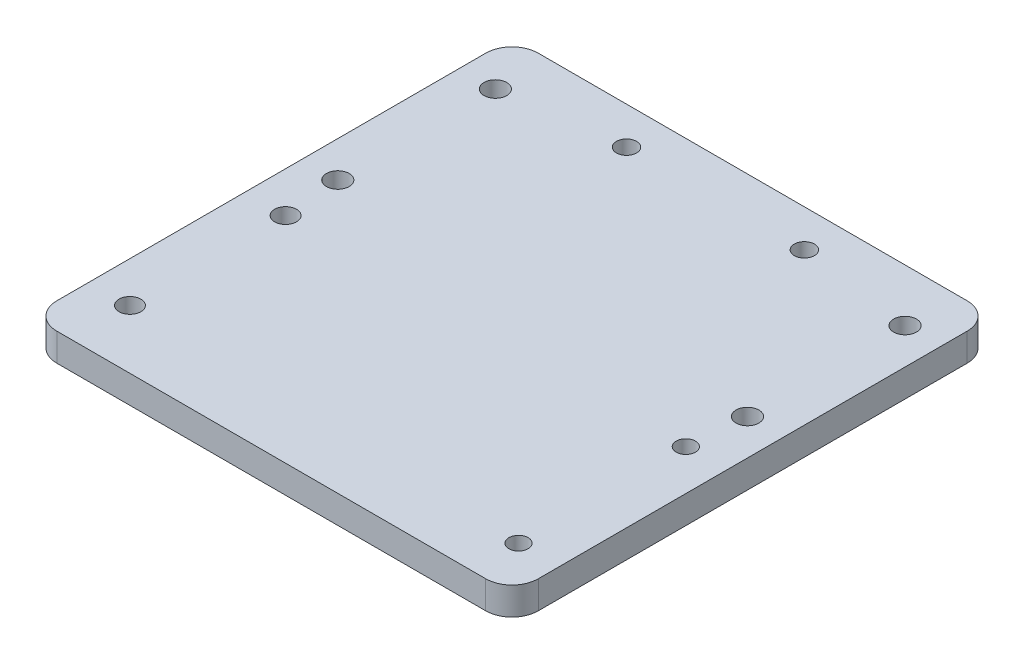
SolidWorks part; units mm, degrees
ref_plane "Front Plane" through (0, 0, 0) normal (0, 0, 1) x (1, 0, 0)
ref_plane "Top Plane" through (0, 0, 0) normal (0, 1, 0) x (1, 0, 0)
ref_plane "Right Plane" through (0, 0, 0) normal (1, 0, 0) x (0, 0, -1)
sketch "Sketch1" plane through (0, 0, 0) normal (0, 1, 0) x (1, 0, 0)
  line L1 (-27.5, 27.5) -> (27.5, 27.5)
  line L2 (-27.5, 27.5) -> (-27.5, -27.5)
  line L3 (-27.5, -27.5) -> (27.5, -27.5)
  line L4 (27.5, 27.5) -> (27.5, -27.5)
  line L5 (-27.5, 27.5) -> (27.5, -27.5) construction
  line L6 (-27.5, -27.5) -> (27.5, 27.5) construction
  point P0 (0, 0)
  dimension "D1" = 55
  dimension "D2" = 55
extrude "Boss-Extrude1" add sketch "Sketch1" along normal blind 3.175
sketch "Sketch2" plane through (0, 3.175, 0) normal (0, 1, 0) x (1, 0, 0)
  line L0 (0, 27.5) -> (0, -27.5) construction
  line L1 (27.5, 27.5) -> (-27.5, 27.5) construction
  line L2 (-27.5, -27.5) -> (27.5, -27.5) construction
  line L3 (-27.5, 27.5) -> (-27.5, -27.5) construction
  circle A0 centre (-23.4, 21.5) radius 1.3
  circle A1 centre (-23.4, 3.5) radius 1.3
  circle A2 centre (23.4, 3.5) radius 1.3
  circle A3 centre (23.4, 21.5) radius 1.3
  point P11 (-22.1, 21.5)
  point P17 (22.1, 21.5)
  dimension "D1" = 2.6
  dimension "D2" = 18
  dimension "D3" = 5.4
  dimension "D4" = 6
extrude "Cut-Extrude1" cut sketch "Sketch2" against normal up to surface (3.175 mm away) up to face at (0, 0, 0)
fillet "Fillet1" radius 3 4 edges at (-27.5, 1.5875, 27.5) (27.5, 1.5875, 27.5) (27.5, 1.5875, -27.5) (-27.5, 1.5875, -27.5)
sketch "Sketch3" plane through (0, 3.175, 0) normal (0, 1, 0) x (1, 0, 0)
  line L0 (-27.5, 0) -> (27.5, 0) construction
  line L1 (-22.865, -3) -> (22.855, -3) construction
  line L2 (-22.865, -3) -> (-22.865, -20.78) construction
  line L3 (-22.865, -20.78) -> (22.855, -22.11) construction
  line L4 (22.855, -3) -> (22.855, -22.11) construction
  line L5 (-27.5, 24.5) -> (-27.5, -24.5) construction
  line L6 (27.5, -24.5) -> (27.5, 24.5) construction
  circle A0 centre (-22.865, -3) radius 1.25
  circle A1 centre (22.855, -3) radius 1.1
  circle A2 centre (22.855, -22.11) radius 1.1
  circle A3 centre (-22.865, -20.78) radius 1.25
  dimension "D1" = 2.5
  dimension "D6" = 2.2
  dimension "D2" = 45.72
  dimension "D3" = 17.78
  dimension "D4" = 19.11
  dimension "D5" = 45.72
  dimension "D7" = 3
extrude "Cut-Extrude2" cut sketch "Sketch3" against normal up to surface (3.175 mm away) up to face at (23.4, 0, -20.2)
sketch "Sketch4" plane through (0, 3.175, 0) normal (0, 1, 0) x (1, 0, 0)
  line L0 (24.5, 27.5) -> (-24.5, 27.5) construction
  line L1 (-10.16, 23.24) -> (10.16, 23.24) construction
  line L2 (-10.16, 23.24) -> (-10.16, 8) construction
  line L3 (-10.16, 8) -> (10.16, 8) construction
  line L4 (10.16, 23.24) -> (10.16, 8) construction
  line L5 (-10.16, 23.24) -> (10.16, 8) construction
  line L6 (-10.16, 8) -> (10.16, 23.24) construction
  line L7 (0, 27.5) -> (0, -27.5) construction
  line L8 (-24.5, -27.5) -> (24.5, -27.5) construction
  circle A0 centre (-10.16, 23.24) radius 1.15
  circle A1 centre (10.16, 23.24) radius 1.15
  point P0 (0, 15.62)
  point P13 (0, 0)
  dimension "D1" = 2.3
  dimension "D2" = 20.32
  dimension "D3" = 15.24
  dimension "D4" = 8
extrude "Cut-Extrude3" cut sketch "Sketch4" against normal up to surface (3.175 mm away) up to face at (-22.865, 0, 22.03)
